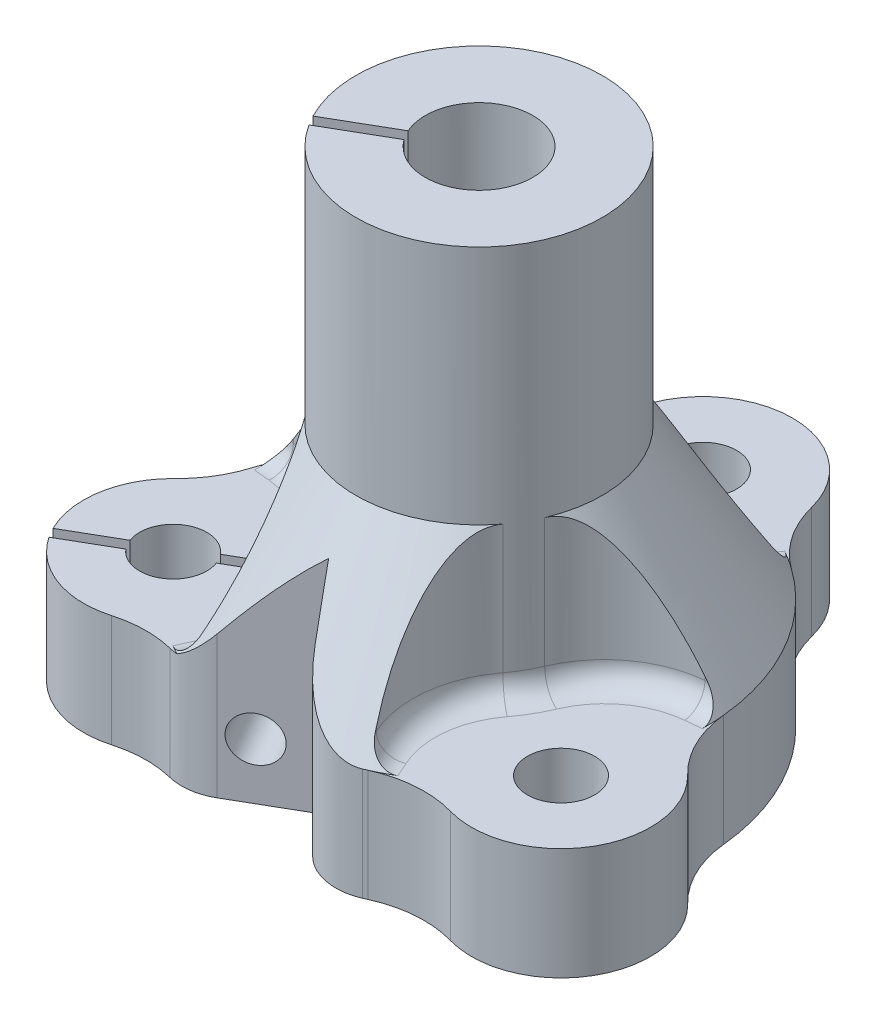
SolidWorks part; units mm, degrees
ref_plane "Front Plane" through (0, 0, 0) normal (0, 0, 1) x (1, 0, 0)
ref_plane "Top Plane" through (0, 0, 0) normal (0, 1, 0) x (1, 0, 0)
ref_plane "Right Plane" through (0, 0, 0) normal (1, 0, 0) x (0, 0, -1)
sketch "Sketch1" plane through (0, 0, 0) normal (0, 1, 0) x (1, 0, 0)
  line L0 (0, -4.8) -> (0, 3.2) construction
  line L1 (-3.5777, 3.2) -> (3.5777, 3.2)
  arc A0 (-7.8384, 18.4) -> (-19.8541, -2.4118) centre (0, 0) ccw construction
  circle A1 centre (0, 20) radius 3
  circle A2 centre (17.3205, -10) radius 3
  circle A3 centre (-17.3205, -10) radius 3
  arc A4 (-3.5777, 3.2) -> (3.5777, 3.2) centre (0, 0) ccw
  arc A6 (7.7573, 21.9556) -> (-7.7573, 21.9556) centre (0, 20) ccw
  arc A7 (15.1354, -17.6958) -> (22.8927, -4.2598) centre (17.3205, -10) ccw
  arc A8 (-22.8927, -4.2598) -> (-15.1354, -17.6958) centre (-17.3205, -10) ccw
  arc A9 (-11.636, 16.2667) -> (-19.9053, 1.9437) centre (0, 0) ccw
  arc A10 (-7.7573, 21.9556) -> (-11.636, 16.2667) centre (-17.4539, 24.4) cw
  arc A11 (-22.8927, -4.2598) -> (-19.9053, 1.9437) centre (-29.858, 2.9156) ccw
  arc A12 (19.8541, -2.4118) -> (7.8384, 18.4) centre (0, 0) ccw construction
  arc A13 (15.1354, -17.6958) -> (8.2694, -18.2104) centre (12.4041, -27.3156) ccw
  arc A14 (7.7573, 21.9556) -> (11.636, 16.2667) centre (17.4539, 24.4) ccw
  arc A15 (19.9053, 1.9437) -> (11.636, 16.2667) centre (0, 0) ccw
  arc A16 (-12.0157, -15.9882) -> (12.0157, -15.9882) centre (0, 0) ccw construction
  arc A17 (-8.2694, -18.2104) -> (8.2694, -18.2104) centre (0, 0) ccw
  arc A18 (19.9053, 1.9437) -> (22.8927, -4.2598) centre (29.858, 2.9156) ccw
  arc A19 (-15.1354, -17.6958) -> (-8.2694, -18.2104) centre (-12.4041, -27.3156) cw
  point P11 (0, 0)
  point P16 (0, 3.2)
  point P23 (0, 0)
  dimension "D1" = 40
  dimension "D2" = 3
  dimension "D3" = 3
  dimension "D4" = 10
  dimension "D5" = 10
  dimension "D6" = 10
extrude "Boss-Extrude1" add sketch "Sketch1" along normal blind 10
sketch "Sketch2" plane through (0, 10, 0) normal (0, 1, 0) x (1, 0, 0)
  circle A0 centre (0, 0) radius 4.8
  arc A1 (-3.5777, 3.2) -> (3.5777, 3.2) centre (0, 0) ccw construction
  circle A2 centre (0, 0) radius 11
  dimension "D1" = 22
extrude "Boss-Extrude2" add sketch "Sketch2" along normal blind 35
sketch "Sketch3" plane through (0, 10, 0) normal (0, 1, 0) x (1, 0, 0)
  line L0 (-6.3998, 8.9467) -> (-11.636, 16.2667)
  line L1 (6.3998, 8.9467) -> (11.636, 16.2667)
  line L2 (10.9479, 1.069) -> (19.9053, 1.9437)
  line L3 (4.5482, -10.0157) -> (8.2694, -18.2104)
  line L4 (-4.5482, -10.0157) -> (-8.2694, -18.2104)
  line L5 (-10.9479, 1.069) -> (-19.9053, 1.9437)
  arc A0 (-11.636, 16.2667) -> (-19.9053, 1.9437) centre (0, 0) ccw
  arc A1 (-6.3998, 8.9467) -> (-10.9479, 1.069) centre (0, 0) ccw
  arc A2 (10.9479, 1.069) -> (6.3998, 8.9467) centre (0, 0) ccw
  arc A3 (19.9053, 1.9437) -> (11.636, 16.2667) centre (0, 0) ccw
  arc A4 (-8.2694, -18.2104) -> (8.2694, -18.2104) centre (0, 0) ccw
  arc A5 (-4.5482, -10.0157) -> (4.5482, -10.0157) centre (0, 0) ccw
extrude "Boss-Extrude3" add sketch "Sketch3" along normal blind 15
chamfer "Chamfer1" distance 15 distance2 10 3 edges at (17.3205, 25, -10) (-17.3205, 25, -10) (0, 25, 20) first distance on face at (16.2873, 11.6667, -9.4035) first distance on face at (-16.2873, 11.6667, -9.4035) first distance on face at (0, 11.6667, 18.8069)
fillet "Fillet1" radius 10 6 edges at (6.3998, 16.75, -8.9467) (-6.3998, 16.75, -8.9467) (4.5482, 16.75, 10.0157) (10.9479, 16.75, -1.069) (-10.9479, 16.75, -1.069) (-4.5482, 16.75, 10.0157)
fillet "Fillet2" radius 2 15 edges at (19.142, 10, -1.8692) (7.9523, 10, 17.5121) (6.8019, 10, 11.5716) (9.5263, 10, 5.5) (-7.9523, 10, 17.5121) (-19.142, 10, -1.8692) (-13.4222, 10, 0.1048) (-9.5263, 10, 5.5) (-11.1898, 10, -15.6429) (-6.6204, 10, -11.6764) (0, 10, -11) (11.1898, 10, -15.6429) (13.4222, 10, 0.1048) (-6.8019, 10, 11.5716) (6.6204, 10, -11.6764)
sketch "Sketch4" plane through (0, 0, 0) normal (0, -1, 0) x (1, 0, 0)
  line L0 (-4.1569, 2.4) -> (-24.2487, 14) construction
  line L1 (-3.8843, 2.82) -> (-23.9852, 14.4252)
  line L2 (-4.3843, 1.9539) -> (-24.4852, 13.5592)
  line L3 (0.25, 0.433) -> (-23.9987, 14.433) construction
  line L4 (0, 0) -> (-24.2487, 14) construction
  line L5 (-0.25, -0.433) -> (-24.4987, 13.567) construction
  arc A0 (-15.1354, 17.6958) -> (-22.8927, 4.2598) centre (-17.3205, 10) ccw construction
  arc A1 (3.5777, -3.2) -> (-3.5777, -3.2) centre (0, 0) ccw construction
  arc A2 (-3.8843, 2.82) -> (-4.3843, 1.9539) centre (0, 0) ccw
  arc A3 (-23.9852, 14.4252) -> (-24.4852, 13.5592) centre (-17.3205, 10) ccw
  dimension "D1" = 0.5
  dimension "D2" = 0.5
extrude "Cut-Extrude1" cut sketch "Sketch4" against normal blind 50
sketch "Sketch5" plane through (0, 0, 0) normal (0, -1, 0) x (1, 0, 0)
  line L0 (-23.9852, 14.4252) -> (-24.4852, 13.5592) construction
  line L1 (-24.2352, 13.9922) -> (0, 0) construction
  line L2 (-8.2694, 18.2104) -> (0, 13.436)
  line L3 (0, 13.436) -> (3.601, 19.6732)
  line L4 (-8.2694, 18.2104) -> (-4.4774, 24.3206)
  line L5 (-4.4774, 24.3206) -> (3.601, 19.6732)
  line L6 (-19.9053, -1.9437) -> (-23.3009, -8.2828)
  line L7 (-19.9053, -1.9437) -> (-11.636, -6.718)
  line L8 (-11.636, -6.718) -> (-15.237, -12.9551)
  line L9 (-23.3009, -8.2828) -> (-15.237, -12.9551)
  arc A0 (8.2694, 18.2104) -> (-8.2694, 18.2104) centre (0, 0) ccw construction
extrude "Cut-Extrude2" cut sketch "Sketch5" against normal blind 50
sketch "Sketch6" plane through (5.818, 0, 10.077) normal (0.5, 0, 0.866) x (0.866, 0, -0.5)
  line L0 (-16.2667, 5) -> (-6.718, 5) construction
  line L1 (-16.2667, 10) -> (-16.2667, 0) construction
  line L2 (-6.718, 19.8459) -> (-6.718, 0) construction
  circle A0 centre (-11.4923, 5) radius 2
extrude "Cut-Extrude3" cut sketch "Sketch6" against normal blind 50
fillet "Fillet3" radius 5 4 edges at (-8.2694, 5, 18.2104) (-19.9053, 5, -1.9437) (3.601, 5, 19.6732) (-15.237, 5, -12.9551)
